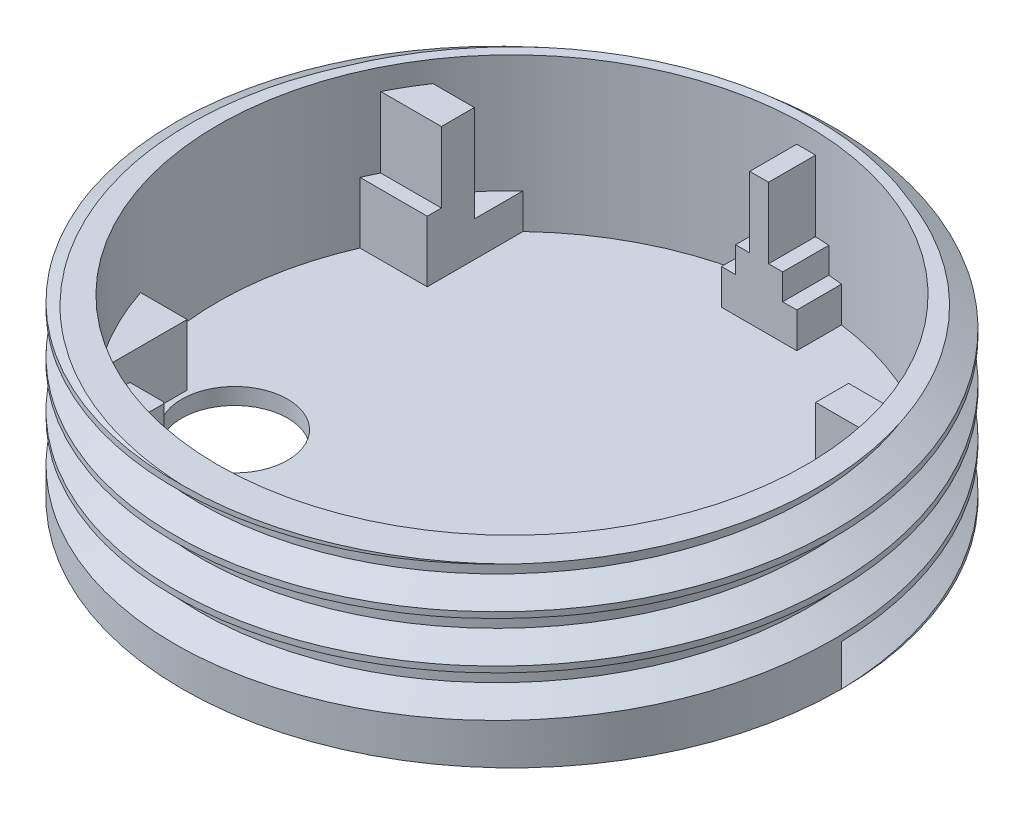
SolidWorks part; units mm, degrees
ref_plane "Front Plane" through (0, 0, 0) normal (0, 0, 1) x (1, 0, 0)
ref_plane "Top Plane" through (0, 0, 0) normal (0, 1, 0) x (1, 0, 0)
ref_plane "Right Plane" through (0, 0, 0) normal (1, 0, 0) x (0, 0, -1)
sketch "Sketch1" plane through (0, 0, 0) normal (0, 1, 0) x (1, 0, 0)
  circle A0 centre (0, 0) radius 14
extrude "Boss-Extrude1" add sketch "Sketch1" along normal blind 7.5
sketch "Sketch2" plane through (0, 0, 0) normal (0, 1, 0) x (1, 0, 0)
  circle A0 centre (0, 0) radius 12.5
extrude "Cut-Extrude1" cut sketch "Sketch2" along normal through all from offset 1
sketch "Sketch3" plane through (0, 1, 0) normal (0, 1, 0) x (1, 0, 0)
  line L0 (10.7163, 5.4) -> (9.5, 5.4) construction
  line L1 (-1, 10.5) -> (1, 10.5)
  line L2 (-1, 10.5) -> (-1, 13.5175)
  line L3 (-1, 13.5175) -> (1, 13.5175)
  line L4 (1, 10.5) -> (1, 13.5175)
  line L5 (9.5, 5.4) -> (12.6254, 5.4)
  line L6 (9.5, 5.4) -> (9.5, 3.4)
  line L7 (9.5, 3.4) -> (12.6254, 3.4)
  line L8 (12.6254, 5.4) -> (12.6254, 3.4)
  line L9 (9.5, 5.4) -> (9.5, 3.4) construction
  line L10 (-1, 10.5) -> (-1.6, 10.5)
  line L11 (-9.9, -3.9) -> (-12.0095, -3.9)
  line L12 (-9.9, -3.9) -> (-9.9, -6.9026)
  line L13 (-9.9, -6.9026) -> (-12.0095, -6.9026)
  line L14 (-12.0095, -3.9) -> (-12.0095, -6.9026)
  line L15 (-8.6, 7) -> (-11.9432, 7)
  line L16 (-8.6, 7) -> (-8.6, 5)
  line L17 (-8.6, 5) -> (-11.9432, 5)
  line L18 (-11.9432, 7) -> (-11.9432, 5)
  line L19 (1, 10.5) -> (1.6, 10.5)
  line L20 (1.6, 10.5) -> (1.6, 12.3972)
  line L21 (-1.6, 10.5) -> (-1.6, 12.3972)
  line L22 (9.5, 5.4) -> (9.5, 8.124)
  line L23 (-8.6, 7) -> (-8.6, 9.0714)
  line L24 (-1.6, 12.3972) -> (-1, 13.5175)
  line L25 (1.6, 12.3972) -> (1, 13.5175)
  line L26 (9.5, 8.124) -> (12.6254, 5.4)
  line L27 (-8.6, 9.0714) -> (-11.9432, 7)
  line L28 (-9.9, -6.3315) -> (-8.4, -6.3315)
  line L29 (-9.9, -7.6315) -> (-9.9, -6.3315)
  line L30 (-8.4, -6.3315) -> (-8.4, -9.2569)
  circle A0 centre (0, 0) radius 12.5 construction
  circle M5 centre (0, 0) radius 12.5
  dimension "D1" = 1.3
  dimension "D2" = 1.5
extrude "Boss-Extrude3" add sketch "Sketch3<3>" along normal blind 1.5 contours L15 L23 M5 | L21 L10 L2 M5 | L19 L20 L4 M5 | L22 L5 M5 | L30 L28 L12 L29 M5 region at (-1.2984, 1, -11.4656) region at (1.2984, 1, -11.4656) region at (-9.207, 1, -7.7155) region at (10.1199, 1, -6.3495) region at (-9.0563, 1, 7.4627)
sketch "Sketch3<3>" plane through (0, 1, 0) normal (0, 1, 0) x (1, 0, 0) same geometry as "Sketch3"
extrude "Boss-Extrude2" add sketch "Sketch3" along normal blind 2.6 contours L13 L12 L11 M5 | L17 L16 L15 M5 | L1 L4 L2 M5 | L6 L7 L5 M5 | L29 L13 M5 | L12 L11 L14 L13 region at (0, 1, -11.4934) region at (-9.7945, 1, -5.922) region at (10.6028, 1, -4.3425) region at (-10.6319, 1, 5.1292) region at (-10.076, 1, 7.1486)
sketch "Sketch4" plane through (0, 1, 0) normal (0, 1, 0) x (1, 0, 0)
  line L0 (9.5059, -2.3939) -> (12.2686, -2.3939)
  line L1 (7.8059, -4.0939) -> (7.8059, -9.7631)
  circle A0 centre (-10.6998, -0.8045) radius 0.3
  circle A1 centre (-10.7027, -2.7082) radius 0.3
  circle A2 centre (9.5059, -4.0939) radius 0.6
  circle A3 centre (9.5059, -4.0939) radius 1.7
  circle A4 centre (0, 0) radius 12.5 construction
  arc M1 (-8.4, -9.2569) -> (12.0287, 3.4) centre (0, 0) ccw
extrude "Boss-Extrude4" add sketch "Sketch4" along normal blind 1.5 contours A3 L1 L0 M1 | A3 A2 region at (9.5811, 1, 6.1301) region at (10.674, 1, 2.9258)
sketch "Sketch5" plane through (0, 1, 0) normal (0, 1, 0) x (1, 0, 0)
  circle A1 centre (-7.435, -4.345) radius 0.5
sketch "Sketch6" plane through (0, 3.6, 0) normal (0, 1, 0) x (1, 0, 0)
  line L0 (-1, 10.5) -> (-0.4, 10.5)
  line L1 (-1, 10.5) -> (1, 10.5) construction
  line L2 (-0.4, 10.5) -> (-0.4, 12.4936)
  line L3 (1, 10.5) -> (0.4, 10.5)
  line L4 (0.4, 10.5) -> (0.4, 12.4936)
  line L5 (-0.4, 10.5) -> (0.4, 10.5)
  line L6 (-8.6, 5) -> (-8.6, 5.6)
  line L7 (-8.6, 7) -> (-8.6, 5) construction
  line L8 (-8.6, 5.6) -> (-8.6, 7)
  line L9 (-8.6, 7) -> (-10.3562, 7)
  line L10 (-8.6, 5.6) -> (-11.1754, 5.6)
  line L11 (9.5, 5.4) -> (9.5, 4.8)
  line L12 (9.5, 5.4) -> (9.5, 3.4) construction
  line L13 (9.5, 4.8) -> (11.5417, 4.8)
  line L14 (9.5, 4.8) -> (9.5, 3.4)
  line L15 (9.5, 3.4) -> (12.0287, 3.4)
  line L16 (9.5, 3.4) -> (12.0287, 3.4) construction
  line L17 (-11.1754, 5.6) -> (-11.1754, 7)
  line L18 (-11.1754, 7) -> (-10.3562, 7)
  line L19 (0.4, 12.4936) -> (0.4, 12.7613)
  line L20 (0.4, 12.7613) -> (-0.4, 12.7613)
  line L21 (-0.4, 12.7613) -> (-0.4, 12.4936)
  line L22 (12.0287, 3.4) -> (12.0287, 4.8)
  line L23 (12.0287, 4.8) -> (11.5417, 4.8)
  circle A0 centre (0, 0) radius 12.5 construction
  line M5 (-1, 10.5) -> (1, 10.5)
  arc M7 (1, 12.4599) -> (-1, 12.4599) centre (0, 0) ccw
  dimension "D1" = 0.6
  dimension "D2" = 0.6
  dimension "D3" = 0.6
  dimension "D4" = 0.6
extrude "Boss-Extrude5" add sketch "Sketch6" along normal blind 3 contours L18 L17 L10 L8 L9 | L4 L2 M5 M7 | L22 L23 L13 L14 L15 region at (0, 3.6, -11.4989) region at (-9.8877, 3.6, -6.3) region at (10.7644, 3.6, -4.1)
sketch "Sketch7" plane through (0, 0, 0) normal (0, -1, 0) x (-1, 0, 0)
  circle A0 centre (7.435, -4.345) radius 2.25
  point P3 (6.875, -5.975)
  point P4 (5.1238, -5.975)
  point P5 (0, 0)
  point P6 (7.435, -4.345)
  point P8 (7.435, -4.345)
  point P9 (0, 0)
  point P10 (7.435, -4.345)
extrude "Cut-Extrude2" cut sketch "Sketch7" against normal up to next
sketch "Sketch8" plane through (0, 0, 0) normal (0, -1, 0) x (-1, 0, 0)
  circle A0 centre (0, 0) radius 12
extrude "Cut-Extrude3" cut sketch "Sketch8" against normal blind 0.3
thread "Thread1" pitch 2 method cut profile "Thread Profile1" start angle 0, offset 0, length 0, pitch 2, diameter 28
ref_plane "Plane1" through (14, 0, 0) normal (0, 0, 1) x (1, 0, 0)
sketch "Thread Profile1" plane through (14, 0, 0) normal (0, 0, 1) x (1, 0, 0)
  line L0 (0, 0) -> (0, 2) construction
  line L11 (0, 0) -> (0, 1.75)
  line L12 (0, 1.75) -> (-1.0825, 1.125)
  line L13 (-1.0825, 1.125) -> (-1.0825, 0.625)
  line L15 (-1.0825, 0.625) -> (0, 0)
  line L17 (-1.0825, 0.875) -> (0, 0.875) construction
  point P2 (0, 0)
  dimension "Pitch" = 2
  dimension "Profile_Angle" = 60
  dimension "Profile_Land" = 0.5
  dimension "Profile_Height" = 1.0825
